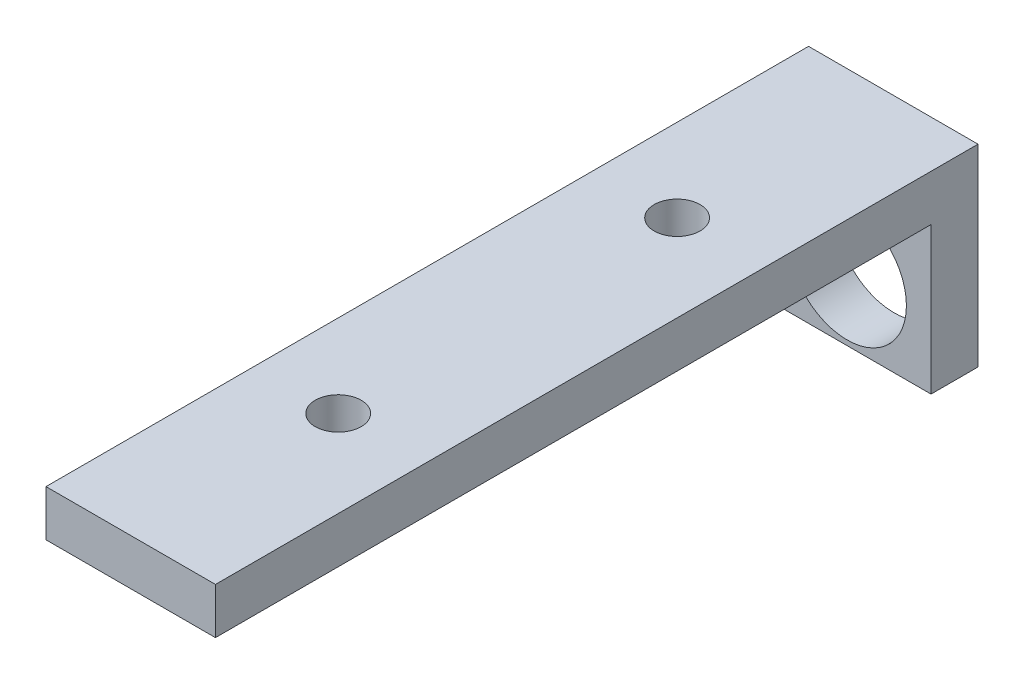
SolidWorks part; units mm, degrees
ref_plane "Front Plane" through (0, 0, 0) normal (0, 0, 1) x (1, 0, 0)
ref_plane "Top Plane" through (0, 0, 0) normal (0, 1, 0) x (1, 0, 0)
ref_plane "Right Plane" through (0, 0, 0) normal (1, 0, 0) x (0, 0, -1)
sketch "Sketch1" plane through (0, 0, 0) normal (1, 0, 0) x (0, 0, -1)
  line L0 (-49.7872, 21.7693) -> (40.2128, 21.7693)
  line L1 (40.2128, 21.7693) -> (40.2128, -1.0078)
  line L2 (40.2128, -1.0078) -> (34.6697, -1.0078)
  line L3 (34.6697, -1.0078) -> (34.6697, 16.327)
  line L4 (34.6697, 16.327) -> (-49.7872, 16.327)
  line L5 (-49.7872, 16.327) -> (-49.7872, 21.7693)
  dimension "D1" = 90
extrude "Boss-Extrude1" add sketch "Sketch1" along normal blind 20
sketch "Sketch2" plane through (0, 16.327, 0) normal (0, -1, 0) x (1, 0, 0)
  circle A0 centre (9.7672, 25.0675) radius 2.7089
extrude "Cut-Extrude1" cut sketch "Sketch2" against normal blind 20
pattern_linear "LPattern1" count 2 spacing 40 along (0, 0, -1) of "Cut-Extrude1"
sketch "Sketch3" plane through (0, 0, -34.6697) normal (0, 0, 1) x (1, 0, 0)
  circle A0 centre (10.0943, 6.5774) radius 7
extrude "Cut-Extrude2" cut sketch "Sketch3" against normal blind 20
